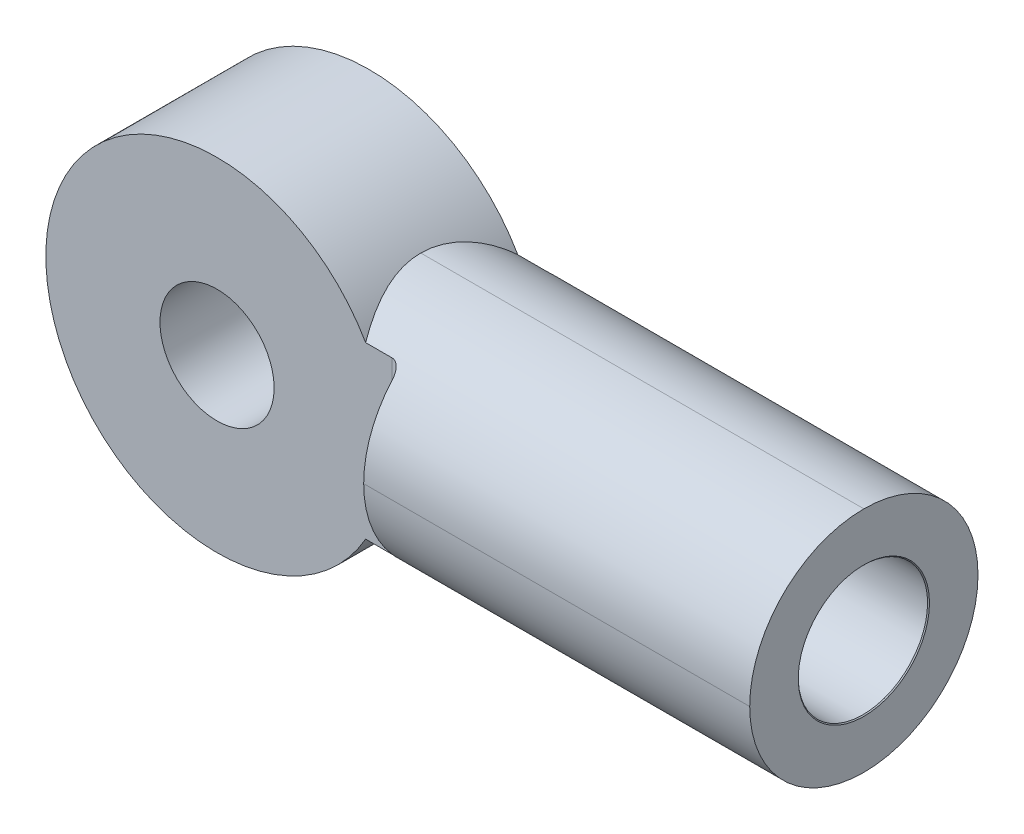
SolidWorks part; units mm, degrees
material "Acier non allié"
ref_plane "Plan de face" through (0, 0, 0) normal (0, 0, 1) x (1, 0, 0)
ref_plane "Plan de dessus" through (0, 0, 0) normal (0, 1, 0) x (1, 0, 0)
ref_plane "Plan de droite" through (0, 0, 0) normal (1, 0, 0) x (0, 0, -1)
sketch "Esquisse1" plane through (0, 0, 0) normal (0, 0, 1) x (1, 0, 0)
  line L1 (3.3541, 3) -> (15, 3)
  line L2 (3.3541, -3) -> (15, -3)
  line L3 (15, 3) -> (15, -3)
  arc A0 (3.3541, 3) -> (3.3541, -3) centre (0, 0) ccw
  dimension "D2" = 9
  dimension "D1" = 6
  dimension "D3" = 15
extrude "Boss.-Extru.2" add sketch "Esquisse1" along normal blind 6
sketch "Esquisse5" plane through (0, 0, 6) normal (0, 0, 1) x (1, 0, 0)
  line L1 (3.3541, 3) -> (4.8541, 3)
  line L2 (3.3541, -3) -> (4.8541, -3)
  line L3 (4.8541, 3) -> (4.8541, -3)
  arc A0 (3.3541, 3) -> (3.3541, -3) centre (0, 0) ccw
  dimension "D1" = 1.5
extrude "Enlèv. mat.-Extru.1" cut sketch "Esquisse5" against normal blind 1
sketch "Esquisse6" plane through (0, 0, 0) normal (0, 0, -1) x (-1, 0, 0)
  line L1 (-3.3541, 3) -> (-4.8541, 3)
  line L2 (-3.3541, -3) -> (-4.8541, -3)
  line L3 (-4.8541, 3) -> (-4.8541, -3)
  arc A0 (-3.3541, -3) -> (-3.3541, 3) centre (0, 0) ccw
  dimension "D1" = 1.5
extrude "Enlèv. mat.-Extru.2" cut sketch "Esquisse6" against normal blind 1
fillet "Congé4" radius 3 4 edges at (9.9271, -3, 6) (9.9271, -3, 0) (9.9271, 3, 0) (9.9271, 3, 6)
fillet "Congé5" radius 0.25 2 edges at (4.8541, 0, 5) (4.8541, 0, 1)
hole_wizard "Dégagement M31" positions "Esquisse7" profile "Esquisse8" hole size "M3" standard "Ansi Metric"
sketch "Esquisse7" plane through (15, 0, 0) normal (1, 0, 0) x (0, 0, -1)
  point P0 (-3, 0)
  dimension "D1" = 3
  dimension "D2" = 3
sketch "Esquisse8" plane through (15, 0, 3) normal (0, 1, 0) x (0, 0, -1)
  line L0 (0, 0) -> (0, 6.0215)
  line L1 (0, 6.0215) -> (1.7, 5)
  line L2 (1.7, 5) -> (1.7, 0.025)
  line L3 (1.7, 0.025) -> (1.725, 0)
  line L5 (1.725, 0) -> (0, 0)
  line L6 (-1.7, 0.025) -> (-1.725, 0) construction
  line L10 (0, 6.0215) -> (-1.7, 5) construction
  line L11 (0, -6.35) -> (0, 107.95) construction
  dimension "Diamètre du perçage" = 3.4
  dimension "Profondeur du perçage" = 5
  dimension "Diamètre du fraisage entrant" = 3.45
  dimension "Angle du fraisage entrant" = 90
  dimension "Angle de pointe" = 118
sketch "Esquisse9" plane through (0, 0, 5) normal (0, 0, 1) x (1, 0, 0)
  circle A0 centre (0, 0) radius 1.5
  dimension "D1" = 3
extrude "Enlèv. mat.-Extru.3" cut sketch "Esquisse9" against normal through all
